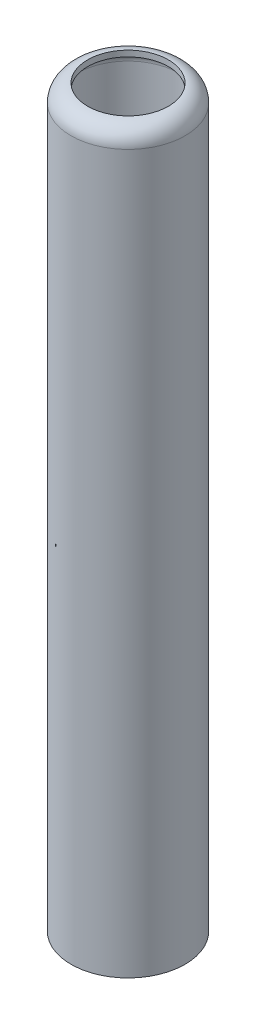
SolidWorks part; units mm, degrees
other "DetailItem1"
material "6061-T6 (SS)"
ref_plane "Front Plane" through (0, 0, 0) normal (0, 0, 1) x (1, 0, 0)
ref_plane "Top Plane" through (0, 0, 0) normal (0, 1, 0) x (1, 0, 0)
ref_plane "Right Plane" through (0, 0, 0) normal (1, 0, 0) x (0, 0, -1)
sketch "Sketch1" plane through (0, 0, 0) normal (0, 1, 0) x (1, 0, 0)
  circle A0 centre (0, 0) radius 14.5
  dimension "D1" = 29
extrude "base" add sketch "Sketch1" along normal blind 186.69
fillet "top-fillet" radius 4.3656 1 edges at (0, 186.69, 14.5)
shell "casing-walls" thickness 1.5 removed face at (0, 0, 14.5)
sketch "Sketch2" plane through (0, 0, 0) normal (0, 1, 0) x (1, 0, 0)
  circle A0 centre (0, 0) radius 10.25
  dimension "D1" = 20.5
extrude "top-hole" cut sketch "Sketch2" against normal through all both and the other way through all
equation "\"grain_number\"= 3'Number of grains in the motor. NOT VALID FOR XL CASINGS"
equation "\"casing_diameter\" = 29mm'Diameter of the casing"
equation "\"casing_length\"= ( IIF ( \"casing_diameter\" = 24mm , \"grain_number\" * 1.25 + 1.48 , 0 ) + IIF ( \"casing_diameter\" = 29mm , \"grain_number\" * 1.75 + 2.10 , 0 ) + IIF ( \"casing_diameter\" = 38mm , \"grain_number\" * 2.30457 + 2.284 , 0 ) + IIF ( \"casing_diameter\" = 54mm , \"grain_number\" * 3.31 + 2.28 , 0 ) ) * 25.4mm'DO NOT TOUCH"
equation "\"D1@Sketch1\"=\"casing_diameter\""
equation "\"D1@base\" = \"casing_length\""
equation "\"fillet_radius\"= 0.171875in'approximate"
equation "\"wall_thickness\"= 1.5mm'Thickness of the casing walls"
equation "\"D1@top-fillet\" = \"fillet_radius\""
equation "\"D1@casing-walls\" = \"wall_thickness\""
equation "\"top_hole_diameter\"= IIF ( \"casing_diameter\" = 24mm , 13mm , 0 ) + IIF ( \"casing_diameter\" = 29mm , 20.5mm , 0 ) + IIF ( \"casing_diameter\" = 38mm , 27mm , 0 ) + IIF ( \"casing_diameter\" = 54mm , 38.3mm , 0 )'DO NOT TOUCH"
equation "\"D1@Sketch2\"=\"top_hole_diameter\""
equation "\"D1@top-hole\" = \"casing_length\" + 1mm"
